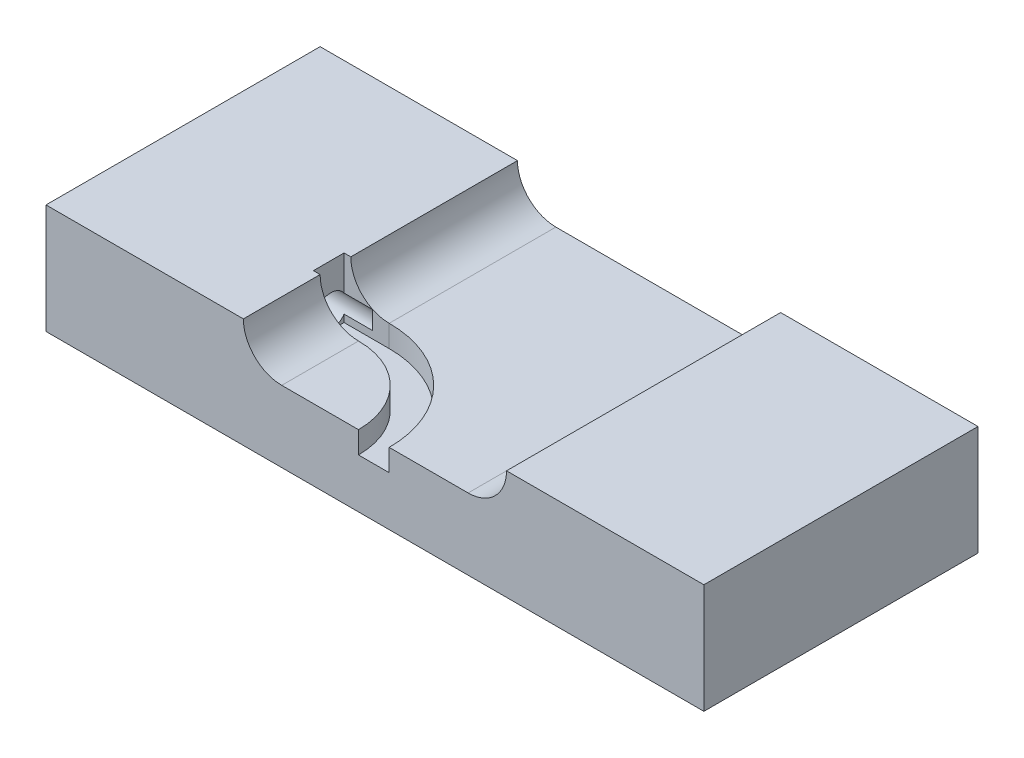
SolidWorks part; units mm, degrees
ref_plane "Front Plane" through (0, 0, 0) normal (0, 0, 1) x (1, 0, 0)
ref_plane "Top Plane" through (0, 0, 0) normal (0, 1, 0) x (1, 0, 0)
ref_plane "Right Plane" through (0, 0, 0) normal (1, 0, 0) x (0, 0, -1)
sketch "Sketch1" plane through (0, 0, 0) normal (0, 1, 0) x (1, 0, 0)
  line L1 (-19.05, -7.9375) -> (19.05, -7.9375)
  line L2 (-19.05, -7.9375) -> (-19.05, 7.9375)
  line L3 (-19.05, 7.9375) -> (19.05, 7.9375)
  line L4 (19.05, -7.9375) -> (19.05, 7.9375)
  line L5 (-19.05, -7.9375) -> (19.05, 7.9375) construction
  line L6 (-19.05, 7.9375) -> (19.05, -7.9375) construction
  point P0 (0, 0)
  dimension "D1" = 38.1
  dimension "D2" = 15.875
extrude "Boss-Extrude1" add sketch "Sketch1" along normal blind 6.35
sketch "Sketch2" plane through (0, 0, -7.9375) normal (0, 0, -1) x (-1, 0, 0)
  line L0 (5.3975, 6.35) -> (-5.3975, 6.35) construction
  line L1 (5.3975, 4.1275) -> (-5.3975, 4.1275)
  line L2 (5.3975, 8.5725) -> (-5.3975, 8.5725)
  line L3 (19.05, 6.35) -> (-19.05, 6.35) construction
  line L4 (-19.05, 0) -> (19.05, 0) construction
  line L6 (19.05, 6.35) -> (19.05, 0) construction
  line L7 (-19.05, 6.35) -> (-19.05, 0) construction
  arc A0 (5.3975, 4.1275) -> (5.3975, 8.5725) centre (5.3975, 6.35) ccw
  arc A1 (-5.3975, 8.5725) -> (-5.3975, 4.1275) centre (-5.3975, 6.35) ccw
  point P2 (0, 6.35)
  dimension "D1" = 6.35
  dimension "D2" = 10.795
  dimension "D3" = 4.445
extrude "Cut-Extrude1" cut sketch "Sketch2" against normal blind 25.4
ref_plane "Plane1" through (0, 4.1275, 0) normal (0, 1, 0) x (1, 0, 0)
sketch "Sketch4" plane through (0, 4.1275, 0) normal (0, 1, 0) x (1, 0, 0)
  line L1 (0.8255, -7.9375) -> (-0.9525, -7.9375)
  line L2 (-5.3975, -3.4925) -> (-8.011, -3.4925)
  line L3 (-8.011, -3.4925) -> (-8.011, -1.7145)
  line L4 (-8.011, -1.7145) -> (-5.3975, -1.7145)
  arc A0 (-0.9525, -7.9375) -> (-5.3975, -3.4925) centre (-5.3975, -7.9375) ccw
  arc A1 (0.8255, -7.9375) -> (-5.3975, -1.7145) centre (-5.3975, -7.9375) ccw
  dimension "D1" = 8.89
  dimension "D2" = 12.446
  dimension "D3" = 2.6135
  dimension "D4" = 1.778
extrude "Cut-Extrude2" cut sketch "Sketch4" along normal through all and the other way blind 1.27
ref_plane "Plane3" through (-19.05, 0, 0) normal (-1, 0, 0) x (0, 0, 1)
sketch "Sketch5" plane through (19.05, 0, 0) normal (1, 0, 0) x (0, 0, -1)
  line L0 (-7.9375, 6.35) -> (-7.9375, 0) construction
  line L1 (-7.9375, 6.35) -> (7.9375, 6.35) construction
  circle A0 centre (-2.4765, 3.81) radius 0.9271
  dimension "D2" = 1.8542
  dimension "D1" = 5.461
  dimension "D3" = 2.54
extrude "Cut-Extrude3" cut sketch "Sketch5" along normal blind 12.7 from surface starting at plane "Plane3"
